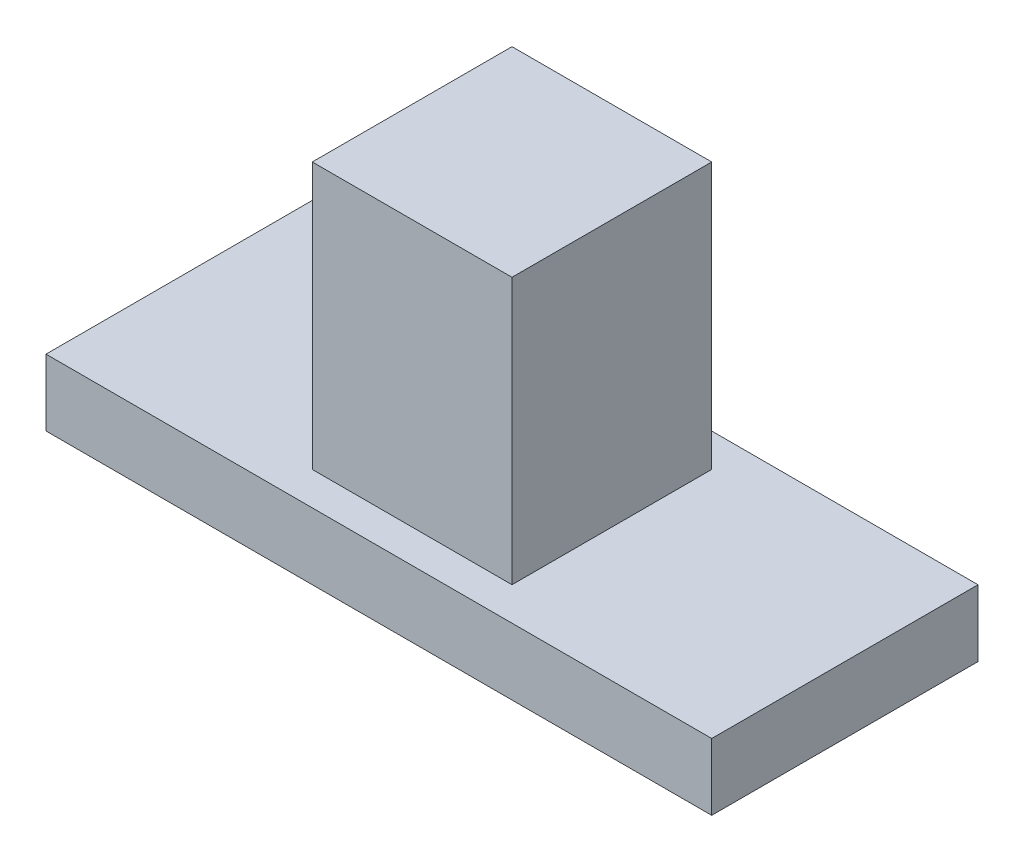
SolidWorks part; units mm, degrees
ref_plane "前视基准面" through (0, 0, 0) normal (0, 0, 1) x (1, 0, 0)
ref_plane "上视基准面" through (0, 0, 0) normal (0, 1, 0) x (1, 0, 0)
ref_plane "右视基准面" through (0, 0, 0) normal (1, 0, 0) x (0, 0, -1)
sketch "草图1" plane through (0, 0, 0) normal (0, 1, 0) x (1, 0, 0)
  line L0 (-4.9469, 0) -> (7.0243, 0) construction
  line L1 (-5, 2.5) -> (5, 2.5)
  line L2 (-5, 2.5) -> (-5, -2.5)
  line L3 (-5, -2.5) -> (5, -2.5)
  line L4 (5, 2.5) -> (5, -2.5)
  line L5 (0, 3.9764) -> (0, -4.0821) construction
  dimension "D1" = 5
  dimension "D2" = 10
extrude "凸台-拉伸1" add sketch "草图1" along normal blind 0.5
sketch "草图2" plane through (0, 0.5, 0) normal (0, 1, 0) x (1, 0, 0)
  line L0 (-5.4747, 0) -> (5.3846, 0) construction
  line L1 (-1.5, 1.5) -> (1.5, 1.5)
  line L2 (-1.5, 1.5) -> (-1.5, -1.5)
  line L3 (-1.5, -1.5) -> (1.5, -1.5)
  line L4 (1.5, 1.5) -> (1.5, -1.5)
  line L5 (0, 3.3379) -> (0, -3.1277) construction
  dimension "D1" = 3
  dimension "D2" = 3
extrude "凸台-拉伸2" add sketch "草图2" along normal blind 0.5
sketch "草图3" plane through (0, 1, 0) normal (0, 1, 0) x (1, 0, 0)
  line L1 (-5, 2.5) -> (5, 2.5)
  line L2 (-5, 2.5) -> (-5, -2.5)
  line L3 (-5, -2.5) -> (5, -2.5)
  line L4 (5, 2.5) -> (5, -2.5)
extrude "凸台-拉伸3" add sketch "草图3" along normal blind 0.5
sketch "草图4" plane through (0, 0, 2.5) normal (0, 0, 1) x (1, 0, 0)
  line L0 (-5, 0) -> (5, 0) construction
  line L1 (-5.959, 2.5) -> (5.2488, 2.5) construction
  line L2 (-5, 1.5) -> (5, 1.5) construction
  line L3 (-5, 1.5) -> (5, 1.5)
  arc A1 (-5, 1.5) -> (5, 1.5) centre (0, -10.5) cw
  dimension "D1" = 1
  dimension "D2" = 2.5
extrude "凸台-拉伸4" add sketch "草图4" against normal up to surface (5 mm away) up to face at (0, 1.25, -2.5)
sketch "草图5" plane through (0, 0, 2.5) normal (0, 0, 1) x (1, 0, 0)
  line L0 (5, 1.5) -> (5, 1) construction
  line L1 (-5, 1.5) -> (-5, 1) construction
  line L2 (-5.4811, 1.25) -> (6.0159, 1.25) construction
  line L3 (-4.75, 2.75) -> (-4.25, 2.75)
  line L4 (-4.75, 2.75) -> (-4.75, 1.3511)
  line L6 (-4.25, 2.75) -> (-4.25, 1.5357)
  line L7 (-3.75, 2.75) -> (-3.75, 1.6974)
  line L8 (-3.75, 2.75) -> (-3.25, 2.75)
  line L9 (-3.25, 2.75) -> (-3.25, 1.8372)
  line L11 (-2.75, 2.75) -> (-2.75, 1.9558)
  line L12 (-2.75, 2.75) -> (-2.25, 2.75)
  line L13 (-2.25, 2.75) -> (-2.25, 2.0538)
  line L15 (-1.75, 2.75) -> (-1.75, 2.1317)
  line L16 (-1.75, 2.75) -> (-1.25, 2.75)
  line L17 (-1.25, 2.75) -> (-1.25, 2.1898)
  line L19 (-0.75, 2.75) -> (-0.75, 2.2283)
  line L20 (-0.75, 2.75) -> (-0.25, 2.75)
  line L21 (-0.25, 2.75) -> (-0.25, 2.2476)
  line L23 (0.25, 2.75) -> (0.25, 2.2476)
  line L24 (0.25, 2.75) -> (0.75, 2.75)
  line L25 (0.75, 2.75) -> (0.75, 2.2283)
  line L27 (1.25, 2.75) -> (1.25, 2.1898)
  line L28 (1.25, 2.75) -> (1.75, 2.75)
  line L29 (1.75, 2.75) -> (1.75, 2.1317)
  line L31 (2.25, 2.75) -> (2.25, 2.0538)
  line L32 (2.25, 2.75) -> (2.75, 2.75)
  line L33 (2.75, 2.75) -> (2.75, 1.9558)
  line L35 (3.25, 2.75) -> (3.25, 1.8372)
  line L36 (3.25, 2.75) -> (3.75, 2.75)
  line L37 (3.75, 2.75) -> (3.75, 1.6974)
  line L39 (4.25, 2.75) -> (4.25, 1.5357)
  line L40 (4.25, 2.75) -> (4.75, 2.75)
  line L41 (4.75, 2.75) -> (4.75, 1.3511)
  arc A0 (5, 1.5) -> (-5, 1.5) centre (0, -10.5) ccw construction
  arc A1 (5, 1.5) -> (-5, 1.5) centre (0, -10.5) ccw construction
  arc A2 (5, 1.25) -> (-5, 1.25) centre (0, -10.75) ccw construction
  arc A3 (-4.75, 1.3511) -> (-4.25, 1.5357) centre (0, -10.75) cw
  arc A4 (-3.75, 1.6974) -> (-3.25, 1.8372) centre (0, -10.75) cw
  arc A5 (-2.75, 1.9558) -> (-2.25, 2.0538) centre (0, -10.75) cw
  arc A6 (-1.75, 2.1317) -> (-1.25, 2.1898) centre (0, -10.75) cw
  arc A7 (-0.75, 2.2283) -> (-0.25, 2.2476) centre (0, -10.75) cw
  arc A8 (0.25, 2.2476) -> (0.75, 2.2283) centre (0, -10.75) cw
  arc A9 (1.25, 2.1898) -> (1.75, 2.1317) centre (0, -10.75) cw
  arc A10 (2.25, 2.0538) -> (2.75, 1.9558) centre (0, -10.75) cw
  arc A11 (3.25, 1.8372) -> (3.75, 1.6974) centre (0, -10.75) cw
  arc A12 (4.25, 1.5357) -> (4.75, 1.3511) centre (0, -10.75) cw
  dimension "D1" = 0.5
  dimension "D2" = 0.25
  dimension "D3" = 1.5
  dimension "D4" = 10
  dimension "D5" = 0.5
extrude "切除-拉伸3" cut sketch "草图5" against normal up to surface (5 mm away) up to face at (0, 1.5, -2.5)
sketch "草图6" plane through (0, 0, 0) normal (0, -1, 0) x (1, 0, 0)
  line L0 (-5.6348, 0) -> (5.5448, 0) construction
  line L1 (0, 3.3379) -> (0, -3.6081) construction
  line L3 (-0.8, 0.8) -> (0.8, 0.8)
  line L4 (-0.8, 0.8) -> (-0.8, -0.8)
  line L5 (-0.8, -0.8) -> (0.8, -0.8)
  line L6 (0.8, 0.8) -> (0.8, -0.8)
  dimension "D1" = 1.6
  dimension "D2" = 1.6
extrude "切除-拉伸4" cut sketch "草图6" against normal blind 1.5
sketch "草图7" plane through (0, 0, 0) normal (0, -1, 0) x (1, 0, 0)
  line L0 (-6.0418, 0) -> (6.0017, 0) construction
  line L1 (-5, 2.5) -> (5, 2.5) construction
  line L2 (5, 2.5) -> (5, -2.5) construction
  line L3 (-5, -2.5) -> (-5, 2.5) construction
  line L5 (0, 3.3716) -> (0, -3.4016) construction
  line L7 (-5, 2.5) -> (5, 2.5)
  line L8 (-5, 2.5) -> (-5, 2)
  line L9 (-5, 2) -> (5, 2)
  line L10 (5, 2.5) -> (5, 2)
  line L11 (-5, -2.5) -> (5, -2.5)
  line L12 (-5, -2.5) -> (-5, -2)
  line L13 (-5, -2) -> (5, -2)
  line L14 (5, -2.5) -> (5, -2)
  dimension "D1" = 4
  dimension "D2" = 10
extrude "切除-拉伸5" cut sketch "草图7" against normal blind 1
sketch "草图8" plane through (0, 0, 0) normal (0, -1, 0) x (1, 0, 0)
  line L1 (-5, 2) -> (5, 2)
  line L2 (-5, 2) -> (-5, -2)
  line L3 (-5, -2) -> (5, -2)
  line L4 (5, 2) -> (5, -2)
extrude "凸台-拉伸5" add sketch "草图8" along normal blind 1
sketch "草图11" plane through (0, 0.5, 0) normal (0, 1, 0) x (1, 0, 0)
  line L0 (-1.5, -1.5) -> (1.5, -1.5) construction
  line L1 (1.5, 1.5) -> (-1.5, 1.5)
  line L2 (1.5, 1.5) -> (1.5, -1.5)
  line L3 (1.5, -1.5) -> (-1.5, -1.5)
  line L4 (-1.5, 1.5) -> (-1.5, -1.5)
  line L5 (-1.5, 1.5) -> (-1.5, -1.5) construction
  line L7 (5, 2) -> (-5, 2)
  line L8 (5, 2) -> (5, -2)
  line L9 (5, -2) -> (-5, -2)
  line L10 (-5, 2) -> (-5, -2)
extrude "切除-拉伸6" cut sketch "草图11" against normal blind 0.5
extrude "切除-拉伸7" cut sketch "草图6<2>" along normal up to next
sketch "草图6<2>" plane through (0, 0, 0) normal (0, -1, 0) x (1, 0, 0) same geometry as "草图6"
sketch "草图12" plane through (0, 1, 0) normal (0, -1, 0) x (1, 0, 0)
  line L1 (-5, 2.5) -> (5, 2.5)
  line L2 (-5, 2.5) -> (-5, -2.5)
  line L3 (-5, -2.5) -> (5, -2.5)
  line L4 (5, 2.5) -> (5, -2.5)
extrude "切除-拉伸8" cut sketch "草图12" against normal through all
sketch "草图13" plane through (0, 1, 0) normal (0, 1, 0) x (1, 0, 0)
  line L1 (-1.5, 1.5) -> (1.5, 1.5)
  line L2 (-1.5, 1.5) -> (-1.5, -1.5)
  line L3 (-1.5, -1.5) -> (1.5, -1.5)
  line L4 (1.5, 1.5) -> (1.5, -1.5)
extrude "凸台-拉伸6" add sketch "草图13" along normal blind 3
sketch "草图14" plane through (0, -1, 0) normal (0, -1, 0) x (1, 0, 0)
  line L0 (-1.5966, 0) -> (1.9234, 0) construction
  line L1 (0, 1.394) -> (0, -1.5165) construction
  line L3 (-0.85, 0.85) -> (0.85, 0.85)
  line L4 (-0.85, 0.85) -> (-0.85, -0.85)
  line L5 (-0.85, -0.85) -> (0.85, -0.85)
  line L6 (0.85, 0.85) -> (0.85, -0.85)
  dimension "D1" = 1.7
  dimension "D2" = 1.7
extrude "切除-拉伸9" cut sketch "草图14" against normal blind 4
